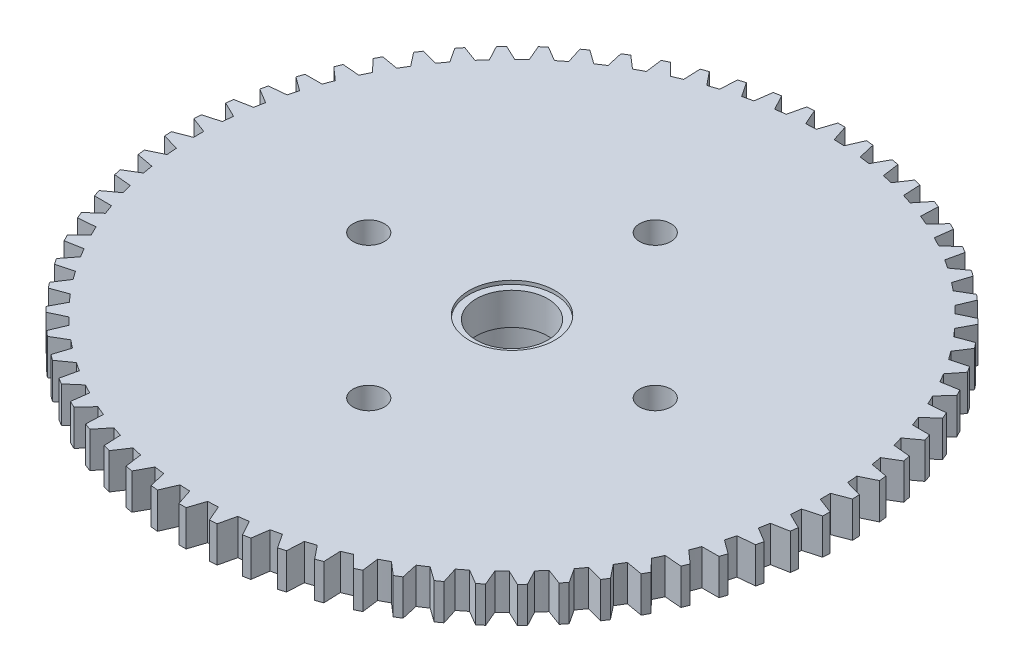
SolidWorks part; units mm, degrees
material "ABS"
ref_plane "Front" through (0, 0, 0) normal (0, 0, 1) x (1, 0, 0)
ref_plane "Top" through (0, 0, 0) normal (0, 1, 0) x (1, 0, 0)
ref_plane "Right" through (0, 0, 0) normal (1, 0, 0) x (0, 0, -1)
sketch "Sketch2" plane through (0, 0, 0) normal (0, 1, 0) x (1, 0, 0)
  circle A0 centre (0, 0) radius 21.875
  circle A1 centre (0, 0) radius 2.5
  dimension "D1" = 43.75
  dimension "D2" = 5
extrude "Boss-Extrude1" add sketch "Sketch2" along normal blind 2.5
ref_plane "Plane1" through (0, 0, 0) normal (0, 1, 0) x (1, 0, 0)
sketch "Sketch3" plane through (0, 0, 0) normal (0, 1, 0) x (1, 0, 0)
  line L0 (0, 21.875) -> (0, -21.875) construction
  line L1 (-21.875, 0) -> (21.875, 0) construction
  line L3 (0, 21.875) -> (0, 23) construction
  line L4 (-0.625, 21.8661) -> (-0.25, 23)
  line L5 (-0.25, 23) -> (0.25, 23)
  line L6 (0.625, 21.8661) -> (0.25, 23)
  circle A0 centre (0, 0) radius 21.875 construction
  arc A1 (-21.875, 0) -> (21.875, 0) centre (0, 0) ccw
  arc A2 (0.625, 21.8661) -> (-0.625, 21.8661) centre (0, 0) ccw
  dimension "D1" = 1.25
  dimension "D2" = 0.25
  dimension "D3" = 23
extrude "Boss-Extrude2" add sketch "Sketch3" along normal blind 2.5 contours L6 L5 L4 A2
pattern_circular "CirPattern1" count 70 over 360 about axis through (0, 2.5, 0) along (0, 1, 0) of "Boss-Extrude2"
sketch "Sketch4" plane through (0, 2.5, 0) normal (0, 1, 0) x (1, 0, 0)
  circle A0 centre (0, 0) radius 3
  circle A1 centre (0, 0) radius 2.5
  circle A2 centre (0, 0) radius 2.5 construction
  dimension "D1" = 0.5
extrude "Cut-Extrude1" cut sketch "Sketch4" against normal blind 0.25
ref_plane "Plane2" through (0, 2.5, 0) normal (0, 1, 0) x (1, 0, 0)
sketch "Sketch5" plane through (0, 2.5, 0) normal (0, 1, 0) x (1, 0, 0)
  line L0 (-34.259, 0) -> (34.259, 0) construction
  line L1 (0, -34.259) -> (0, 34.259) construction
  circle A0 centre (0, 10) radius 1.09
  point P6 (0, 0)
  dimension "D1" = 10
  dimension "D2" = 2.18
extrude "Cut-Extrude2" cut sketch "Sketch5" against normal up to surface (2.5 mm away) up to face at (0, 0, 0)
pattern_circular "CirPattern2" count 4 over 360 about axis through (0, 2.25, 0) along (0, 1, 0) of "Cut-Extrude2"
sketch "Sketch6" plane through (0, 0, 0) normal (0, -1, 0) x (-1, 0, 0)
  circle A0 centre (0, 0) radius 3.15
  circle A1 centre (0, 0) radius 2.8
  dimension "D1" = 6.3
  dimension "D2" = 5.6
extrude "Boss-Extrude3" add sketch "Sketch6" along normal blind 3
